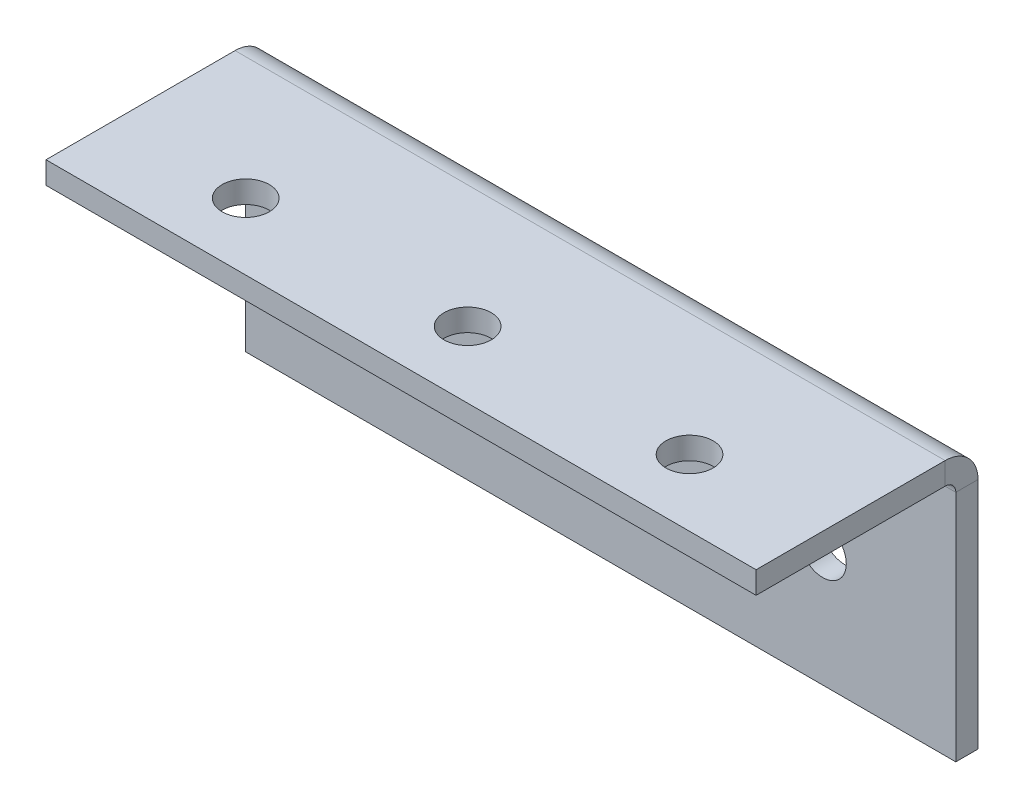
SolidWorks part; units mm, degrees
note: The reader was unsure of these and kept them because the rebuilt part matched: flange length of "Edge-Flange1".
ref_plane "Front" through (0, 0, 0) normal (0, 0, 1) x (1, 0, 0)
ref_plane "Top" through (0, 0, 0) normal (0, 1, 0) x (1, 0, 0)
ref_plane "Right" through (0, 0, 0) normal (1, 0, 0) x (0, 0, -1)
sketch "Sketch1" plane through (0, 0, 0) normal (0, 0, 1) x (1, 0, 0)
  line L1 (0, 0) -> (101.6, 0)
  line L2 (0, 0) -> (0, 38.1)
  line L3 (0, 38.1) -> (101.6, 38.1)
  line L4 (101.6, 0) -> (101.6, 38.1)
  dimension "D1" = 101.6
  dimension "D2" = 38.1
base flange "Base-Flange1" sketch "Sketch1" thickness 3.175 reverse thickness direction no parameters "D1"=1.524
edge flange "Edge-Flange1" sketch "Sketch8" flange angle 90 flange length 31.75 flange position material inside bend radius 1.524 thickness 3.175 relief rectangular parameters "D6"=10
sketch "Sketch8" plane through (0, 38.1, 0) normal (0, 1, 0) x (-1, 0, 0)
  line L0 (-101.6, 0) -> (0, 0) construction
  line L1 (-101.6, 0) -> (0, 0)
  line L2 (-101.6, 0) -> (-101.6, 28.575)
  line L3 (-101.6, 28.575) -> (0, 28.575)
  line L4 (0, 28.575) -> (0, 0)
bend "EdgeBend1" bend radius 1.524 bend angle 90 parameters "D5"=1
hole_wizard "1/4 Clearance Hole1" positions "3DSketch1" profile "Sketch9" hole size "1/4" standard "ANSI Inch" end condition up to next
sketch3d "3DSketch1"
  line L0 (101.6, 0, 0) -> (101.6, 33.401, 0) construction
  line L1 (101.6, 16.7005, 0) -> (82.55, 16.7005, 0) construction
  line L3 (0, 34.925, 28.575) -> (101.6, 34.925, 28.575) construction
  line L4 (101.6, 34.925, 28.575) -> (101.6, 34.925, 1.524) construction
  point P0 (82.55, 16.7005, 0)
  point P2 (50.8, 16.7005, 0)
  point P4 (19.05, 16.7005, 0)
  point P6 (82.55, 34.925, 19.05)
  point P8 (50.8, 34.925, 19.05)
  point P10 (19.05, 34.925, 19.05)
  dimension "D1" = 31.75
  dimension "D2" = 31.75
  dimension "D3" = 31.75
  dimension "D4" = 31.75
  dimension "D5" = 19.05
  dimension "D6" = 9.525
  dimension "D7" = 19.05
sketch "Sketch9" plane through (82.55, 16.7005, 0) normal (1, 0, 0) x (0, -1, 0)
  line L0 (0, 0) -> (0, 3.175)
  line L1 (0, 3.175) -> (3.3782, 3.175)
  line L2 (3.3782, 3.175) -> (3.3782, 0)
  line L5 (3.3782, 0) -> (0, 0)
  line L11 (0, -6.35) -> (0, 107.95) construction
  dimension "Thru Hole Dia." = 6.7564
  dimension "Thru Hole Depth" = 3.175
sketch "Bend-Lines1" plane through (0, 0, 0) normal (0, 1, 0) x (1, 0, 0)
sketch "Bounding-Box1" plane through (0, 0, 0) normal (0, 1, 0) x (1, 0, 0)
sheet metal parameters "Sheet-Metal8" thickness 3.175 parameters "D1"=1.524
flat pattern "Flat-Pattern8" [suppressed]
sketch "Bend-Lines2" plane through (0, 0, 0) normal (0, 1, 0) x (1, 0, 0)
sketch "Bounding-Box2" [suppressed] plane through (0, 0, 0) normal (0, 1, 0) x (1, 0, 0)
sheet metal parameters "Sheet-Metal9" thickness 3.175 parameters "D1"=1.524
flat pattern "Flat-Pattern8" [suppressed]
sketch "Bend-Lines2" plane through (0, 0, 0) normal (0, 1, 0) x (1, 0, 0)
sketch "Bounding-Box2" [suppressed] plane through (0, 0, 0) normal (0, 1, 0) x (1, 0, 0)
bend of the flat pattern "Flatten-<EdgeBend1>1"
sheet metal parameters "Sheet-Metal10" thickness 3.175 parameters "D1"=1.524
flat pattern "Flat-Pattern8" [suppressed]
sketch "Bend-Lines2" plane through (0, 0, 0) normal (0, 1, 0) x (1, 0, 0)
sketch "Bounding-Box2" [suppressed] plane through (0, 0, 0) normal (0, 1, 0) x (1, 0, 0)
bend of the flat pattern "Flatten-<EdgeBend1>1"
